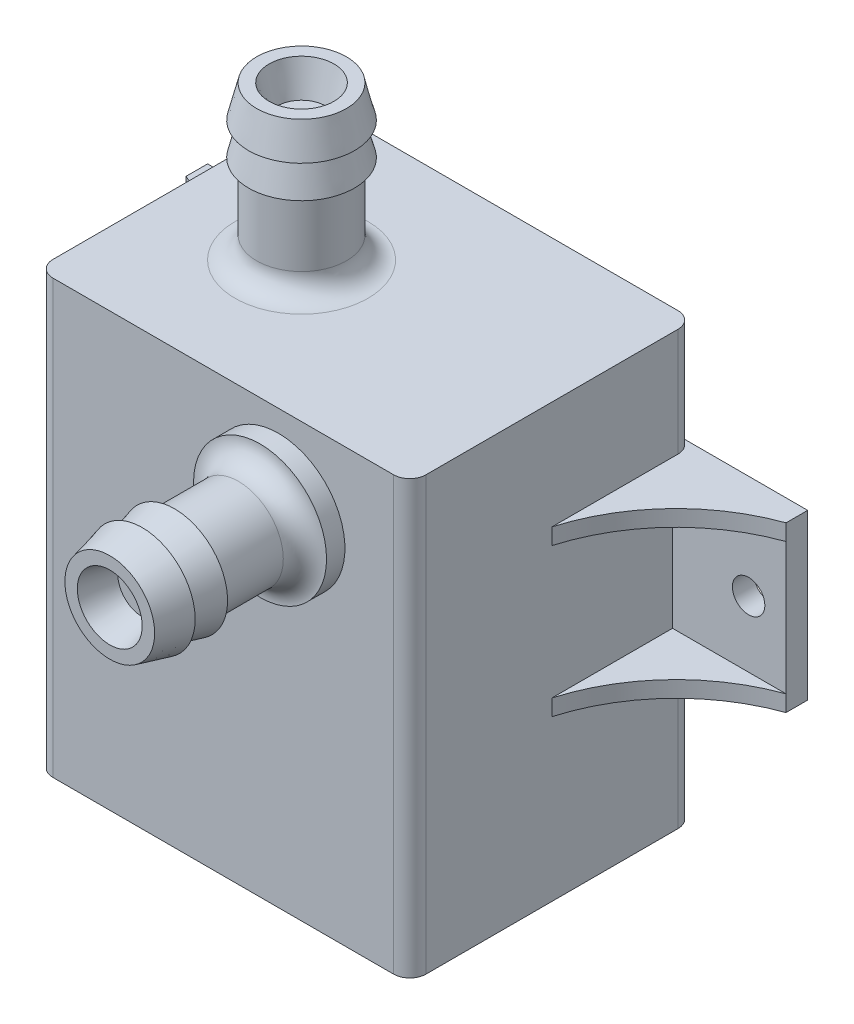
SolidWorks part; units mm, degrees
ref_plane "Front Plane" through (0, 0, 0) normal (0, 0, 1) x (1, 0, 0)
ref_plane "Top Plane" through (0, 0, 0) normal (0, 1, 0) x (1, 0, 0)
ref_plane "Right Plane" through (0, 0, 0) normal (1, 0, 0) x (0, 0, -1)
sketch "Sketch1" plane through (0, 0, 0) normal (0, 0, 1) x (1, 0, 0)
  line L1 (17.25, 20) -> (-17.25, 20)
  line L2 (17.25, 20) -> (17.25, -20)
  line L3 (17.25, -20) -> (-17.25, -20)
  line L4 (-17.25, 20) -> (-17.25, -20)
  line L5 (17.25, 20) -> (-17.25, -20) construction
  line L6 (17.25, -20) -> (-17.25, 20) construction
  point P0 (0, 0)
  dimension "D1" = 40
  dimension "D2" = 34.5
extrude "Boss-Extrude1" add sketch "Sketch1" along normal blind 26.3
fillet "Fillet1" radius 1.5 4 edges at (17.25, 0, 0) (-17.25, 0, 0) (-17.25, 0, 26.3) (17.25, 0, 26.3)
sketch "Sketch2" plane through (0, 20, 0) normal (0, 1, 0) x (1, 0, 0)
  line L0 (15.75, 0) -> (-15.75, 0) construction
  circle A0 centre (-5.7126, -13.35) radius 4.15
  circle A1 centre (-5.7126, -13.35) radius 3
  dimension "D1" = 8.3
  dimension "D3" = 6
  dimension "D2" = 9.2
extrude "Boss-Extrude2" add sketch "Sketch2" along normal blind 14.2
sketch "Sketch3" plane through (0, 34.2, 0) normal (0, 1, 0) x (1, 0, 0)
  circle A0 centre (-5.7126, -13.35) radius 4.15 construction
  circle A1 centre (-5.7126, -13.35) radius 4.15
  circle A2 centre (-5.7126, -13.35) radius 3 construction
  circle A3 centre (-5.7126, -13.35) radius 3
extrude "Boss-Extrude3" add sketch "Sketch3" against normal blind 3 draft 14 draft outward yes
sketch "Sketch4" plane through (0, 31.2, 0) normal (0, -1, 0) x (1, 0, 0)
  circle A0 centre (-5.7126, 13.35) radius 4.15 construction
  circle A1 centre (-5.7126, 13.35) radius 4.15
extrude "Boss-Extrude4" add sketch "Sketch4" along normal blind 3 draft 14 draft outward yes
sketch "Sketch5" plane through (0, 0, 26.3) normal (0, 0, 1) x (1, 0, 0)
  line L0 (15.75, 20) -> (-15.75, 20) construction
  line L1 (17.25, 20) -> (17.25, -20) construction
  circle A0 centre (5.1, 11.85) radius 4.15
  circle A1 centre (5.1, 11.85) radius 3
  dimension "D1" = 8.3
  dimension "D2" = 6
  dimension "D3" = 4
  dimension "D4" = 8
extrude "Boss-Extrude5" add sketch "Sketch5" along normal blind 15.6
sketch "Sketch6" plane through (0, 0, 26.3) normal (0, 0, 1) x (1, 0, 0)
  circle A0 centre (5.1, 11.85) radius 6.15
  dimension "D1" = 12.3
extrude "Boss-Extrude6" add sketch "Sketch6" along normal blind 1.7
fillet "Fillet2" radius 2 2 edges at (-5.7126, 20, 17.5) (9.25, 11.85, 28)
sketch "Sketch7" plane through (0, 0, 41.9) normal (0, 0, 1) x (1, 0, 0)
  circle A0 centre (5.1, 11.85) radius 3 construction
  circle A1 centre (5.1, 11.85) radius 4.15
  circle A2 centre (5.1, 11.85) radius 4.15
  circle A3 centre (5.1, 11.85) radius 3
  dimension "D1" = 0
extrude "Boss-Extrude7" add sketch "Sketch7" against normal blind 3 draft 14 draft outward yes
sketch "Sketch8" plane through (0, 0, 38.9) normal (0, 0, -1) x (-1, 0, 0)
  circle A0 centre (-5.1, 11.85) radius 4.15 construction
  circle A1 centre (-5.1, 11.85) radius 4.15
extrude "Boss-Extrude8" add sketch "Sketch8" along normal blind 3 draft 14 draft outward yes
sketch "Sketch9" plane through (0, -20, 0) normal (0, -1, 0) x (1, 0, 0)
  line L0 (-13.4, 6.2246) -> (-17.25, 6.2246) construction
  line L1 (-13.4, 4.0746) -> (-17.25, 4.0746)
  line L2 (-13.4, 8.3746) -> (-17.25, 8.3746)
  line L3 (-17.25, 24.8) -> (-17.25, 1.5) construction
  line L4 (-17.25, 8.3746) -> (-17.25, 4.0746)
  arc A0 (-13.4, 4.0746) -> (-13.4, 8.3746) centre (-13.4, 6.2246) ccw
  point P2 (-15.9573, 6.2246)
  dimension "D1" = 4.3
  dimension "D2" = 6
extrude "Boss-Extrude9" add sketch "Sketch9" along normal blind 3
sketch "Sketch10" plane through (0, 0, 0) normal (0, 0, -1) x (-1, 0, 0)
  line L0 (0, 0) -> (0, 15.9156) construction
  line L1 (17.25, 20) -> (17.25, -20) construction
  line L2 (17.25, 10) -> (27.75, 10)
  line L3 (17.25, 10) -> (17.25, -5.2)
  line L4 (17.25, -5.2) -> (27.75, -5.2)
  line L5 (27.75, 10) -> (27.75, -5.2)
  line L6 (-15.75, 20) -> (15.75, 20) construction
  line L7 (-27.75, 10) -> (-27.75, -5.2)
  line L8 (-17.25, -5.2) -> (-27.75, -5.2)
  line L9 (-17.25, 10) -> (-17.25, -5.2)
  line L10 (-17.25, 10) -> (-27.75, 10)
  circle A0 centre (24.6662, 2.4) radius 1.5
  circle A1 centre (-24.2855, 2.4) radius 1.5
  dimension "D4" = 3
  dimension "D1" = 10
  dimension "D2" = 15.2
  dimension "D3" = 10.5
extrude "Boss-Extrude10" add sketch "Sketch10" against normal blind 2
sketch "Sketch11" plane through (-17.25, 0, 0) normal (1, 0, 0) x (0, 0, -1)
  line L4 (0, 10) -> (-1.5, 10)
  line L5 (-1.5, 10) -> (-1.5, -5.2)
  line L6 (-1.5, -5.2) -> (0, -5.2)
  line L7 (0, -5.2) -> (0, 10)
  line L8 (0, 10) -> (-1.5, 10)
  line L9 (-1.5, 10) -> (-1.5, -5.2)
  line L10 (-1.5, -5.2) -> (0, -5.2)
  line L11 (0, -5.2) -> (0, 10)
  dimension "D1" = 0
extrude "Boss-Extrude11" add sketch "Sketch11" along normal blind 36
sketch "Sketch12" plane through (0, -5.2, 0) normal (0, -1, 0) x (1, 0, 0)
  line L0 (0, 0) -> (0, -14.4326) construction
  line L1 (-17.25, 24.8) -> (-17.25, 8.3746) construction
  line L2 (-17.25, 13.15) -> (-17.25, 2)
  line L3 (-17.25, 2) -> (-27.75, 2)
  line L4 (17.25, 2) -> (27.75, 2)
  line L5 (17.25, 13.15) -> (17.25, 2)
  arc A0 (-27.75, 2) -> (-17.25, 13.15) centre (-33.4001, 17.8397) ccw
  arc A1 (27.75, 2) -> (17.25, 13.15) centre (33.4001, 17.8397) cw
extrude "Boss-Extrude12" add sketch "Sketch12" against normal blind 1.5
sketch "Sketch13" plane through (0, 10, 0) normal (0, 1, 0) x (1, 0, 0)
  line L2 (-17.25, -13.15) -> (-17.25, -2)
  line L3 (-17.25, -2) -> (-27.75, -2)
  line L4 (-17.25, -13.15) -> (-17.25, -2)
  line L5 (-17.25, -2) -> (-27.75, -2)
  line L6 (27.75, -2) -> (17.25, -2)
  line L7 (17.25, -2) -> (17.25, -13.15)
  line L8 (27.75, -2) -> (17.25, -2)
  line L9 (17.25, -2) -> (17.25, -13.15)
  arc A1 (-17.25, -13.15) -> (-27.75, -2) centre (-33.4001, -17.8397) ccw
  arc A2 (-17.25, -13.15) -> (-27.75, -2) centre (-33.4001, -17.8397) ccw
  arc A3 (27.75, -2) -> (17.25, -13.15) centre (33.4001, -17.8397) ccw
  arc A4 (27.75, -2) -> (17.25, -13.15) centre (33.4001, -17.8397) ccw
  dimension "D1" = 0
  dimension "D2" = 0
extrude "Boss-Extrude14" add sketch "Sketch13" against normal blind 1.5
